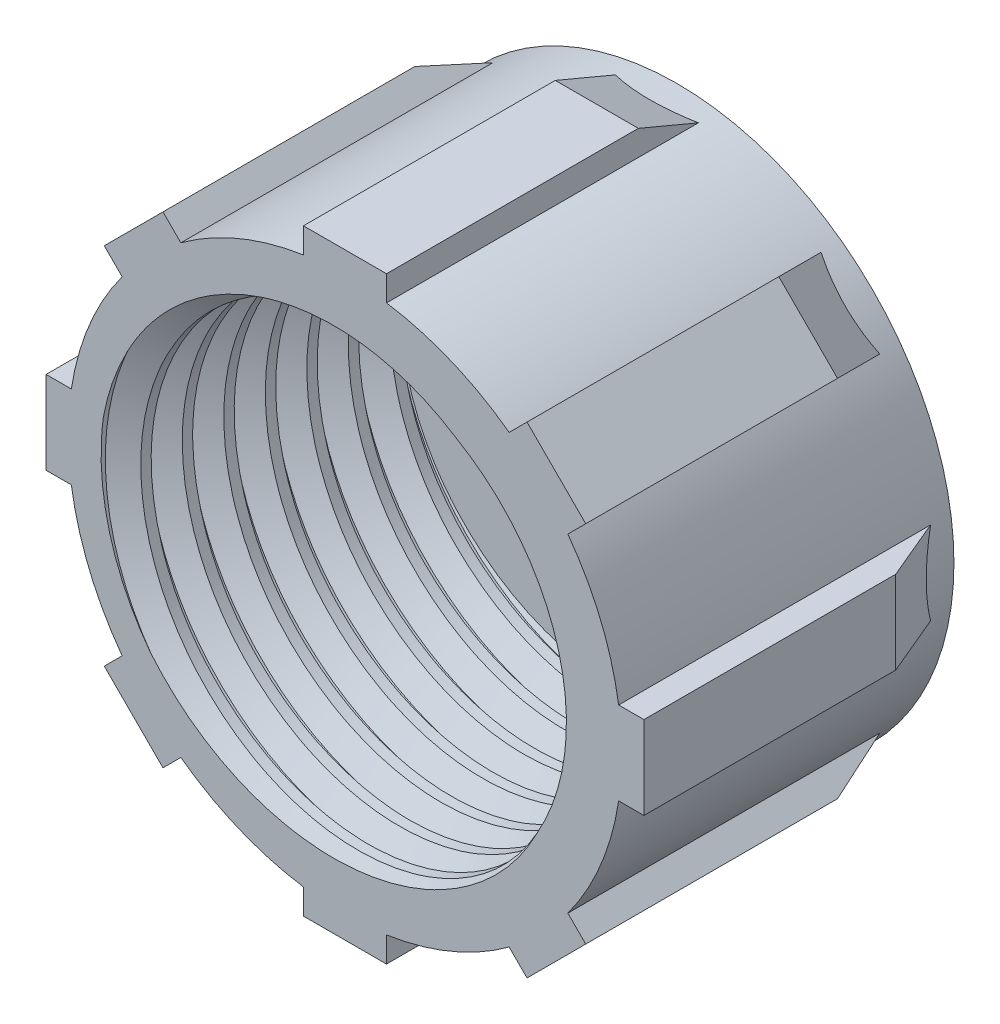
SolidWorks part; units mm, degrees
ref_plane "Front Plane" through (0, 0, 0) normal (0, 0, 1) x (1, 0, 0)
ref_plane "Top Plane" through (0, 0, 0) normal (0, 1, 0) x (1, 0, 0)
ref_plane "Right Plane" through (0, 0, 0) normal (1, 0, 0) x (0, 0, -1)
sketch "Sketch1" plane through (0, 0, 0) normal (0, 0, 1) x (1, 0, 0)
  circle A0 centre (0, 0) radius 10
  dimension "D1" = 20
extrude "Boss-Extrude1" add sketch "Sketch1" along normal blind 12
sketch "Sketch2" plane through (0, 0, 12) normal (0, 0, 1) x (1, 0, 0)
  circle A0 centre (0, 0) radius 8
  dimension "D1" = 16
extrude "Cut-Extrude1" cut sketch "Sketch2" against normal blind 10
sketch "Sketch3" plane through (0, 0, 2) normal (0, 0, 1) x (1, 0, 0)
  circle A0 centre (0, 0) radius 5.5
  dimension "D1" = 11
extrude "Cut-Extrude2" cut sketch "Sketch3" against normal blind 10
thread "Thread1" pitch 1.5 method cut profile "Thread Profile1" start angle 0, offset 5, length 0, pitch 1.5, diameter 16
ref_plane "Plane1" through (-8, 0, 17) normal (0, -1, 0) x (-1, 0, 0)
sketch "Thread Profile1" plane through (-8, 0, 17) normal (0, -1, 0) x (-1, 0, 0)
  line L0 (0, 0) -> (0, 1.5) construction
  line L1 (0, 0) -> (0.8119, 0.4687)
  line L2 (0.8119, 0.4687) -> (0.8119, 0.6562)
  line L3 (0.8119, 0.6562) -> (0, 1.125)
  line L4 (0.8119, 0.5625) -> (0, 0.5625) construction
  line L11 (0, 0) -> (0, 1.125)
  point P2 (0, 0)
  dimension "Pitch" = 1.5
  dimension "Profile_Angle" = 60
  dimension "Profile_Land" = 0.1875
  dimension "Profile_Height" = 0.8119
sketch "Sketch6" plane through (0, 0, 0) normal (1, 0, 0) x (0, 0, -1)
  line L0 (0, 10) -> (-12, 10) construction
  line L1 (-1, 10) -> (-12, 10)
  line L2 (-1, 10) -> (-2.9026, 10.8)
  line L3 (-2.9026, 10.8) -> (-12, 10.8)
  line L4 (-12, 10.8) -> (-12, 10)
  line L5 (-1, 10) -> (-0.1388, 9.6379)
  line L6 (-0.1388, 9.6379) -> (-12, 9.6379)
  line L7 (-12, 10) -> (-12, -10) construction
  line L8 (-12, 9.6379) -> (-12, 10)
  dimension "D1" = 11
  dimension "D2" = 0.8
  dimension "D3" = 0.3621
extrude "Boss-Extrude2" add sketch "Sketch6" along normal blind 1.5 and the other way blind 1.5 contours L3 L4 L1 L2 | L8 L6 L5 L1 region at (0, 9.8167, 6.282) region at (0, 10.3874, 6.9606)
pattern_circular "CirPattern1" count 8 over 360 about axis through (0, 0, -8) along (0, 0, 1) of "Boss-Extrude2" reverse direction yes
